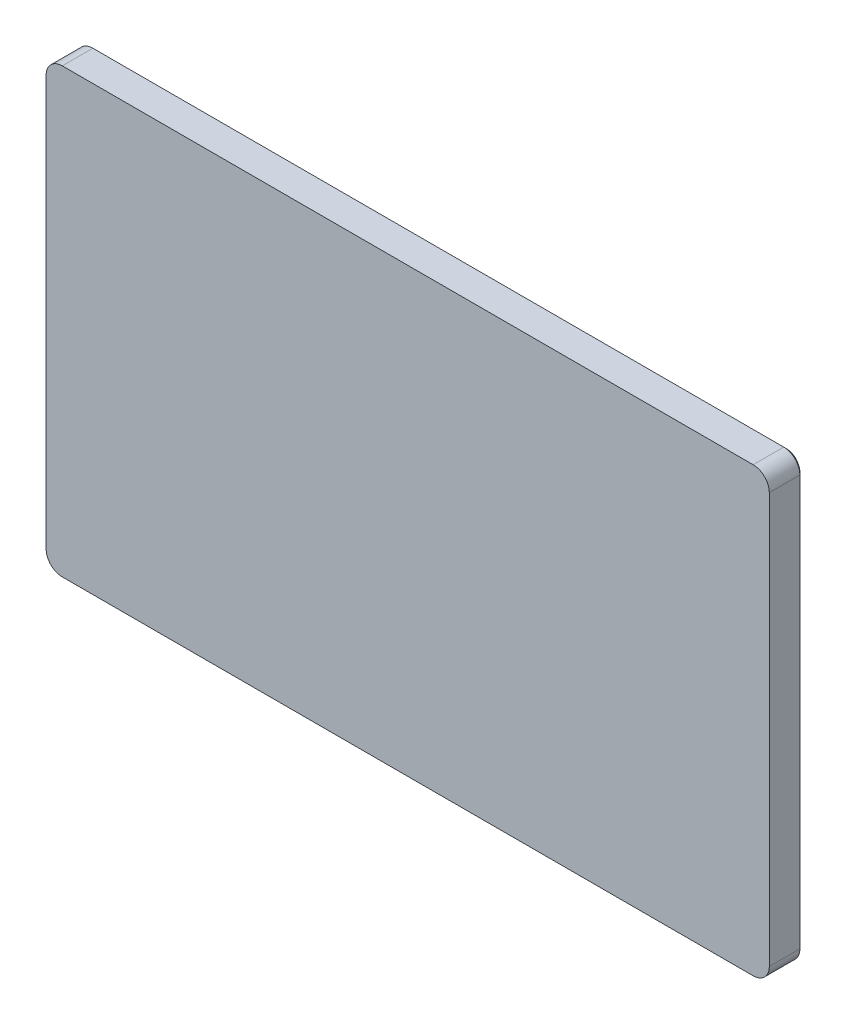
SolidWorks part; units mm, degrees
ref_plane "Front" through (0, 0, 0) normal (0, 0, 1) x (1, 0, 0)
ref_plane "Top" through (0, 0, 0) normal (0, 1, 0) x (1, 0, 0)
ref_plane "Right" through (0, 0, 0) normal (1, 0, 0) x (0, 0, -1)
sketch "Sketch1" plane through (0, 0, 0) normal (0, 0, 1) x (1, 0, 0)
  line L0 (86.5, 49) -> (86.5, -49) construction
  line L5 (82.5, -53) -> (-82.5, -53) construction
  line L6 (-86.5, -49) -> (-86.5, 49) construction
  line L7 (-82.5, 53) -> (82.5, 53) construction
  line L8 (86.5, 49) -> (86.5, -49) construction
  line L9 (82.5, -53) -> (-82.5, -53) construction
  line L10 (-86.5, -49) -> (-86.5, 49) construction
  line L11 (-82.5, 53) -> (82.5, 53) construction
  line L12 (-82.5, 52.85) -> (82.5, 52.85)
  line L13 (86.35, 49) -> (86.35, -49)
  line L14 (82.5, -52.85) -> (-82.5, -52.85)
  line L15 (-86.35, -49) -> (-86.35, 49)
  arc A0 (86.5, 49) -> (82.5, 53) centre (82.5, 49) ccw construction
  arc A1 (82.5, -53) -> (86.5, -49) centre (82.5, -49) ccw construction
  arc A2 (-86.5, -49) -> (-82.5, -53) centre (-82.5, -49) ccw construction
  arc A3 (-82.5, 53) -> (-86.5, 49) centre (-82.5, 49) ccw construction
  arc A4 (86.5, 49) -> (82.5, 53) centre (82.5, 49) ccw construction
  arc A5 (82.5, -53) -> (86.5, -49) centre (82.5, -49) ccw construction
  arc A6 (-86.5, -49) -> (-82.5, -53) centre (-82.5, -49) ccw construction
  arc A7 (-82.5, 53) -> (-86.5, 49) centre (-82.5, 49) ccw construction
  arc A8 (86.35, 49) -> (82.5, 52.85) centre (82.5, 49) ccw
  arc A9 (82.5, -52.85) -> (86.35, -49) centre (82.5, -49) ccw
  arc A10 (-86.35, -49) -> (-82.5, -52.85) centre (-82.5, -49) ccw
  arc A11 (-82.5, 52.85) -> (-86.35, 49) centre (-82.5, 49) ccw
  dimension "D1" = 0.15
extrude "Boss-Extrude1" add sketch "Sketch1" along normal up to surface (7.9 mm away)
chamfer "Chamfer1" distance 0.6 angle 45 8 edges at (86.35, 0, 0) (85.2224, 51.7224, 0) (85.2224, -51.7224, 0) (0, 52.85, 0) (0, -52.85, 0) (-85.2224, 51.7224, 0) (-85.2224, -51.7224, 0) (-86.35, 0, 0)
